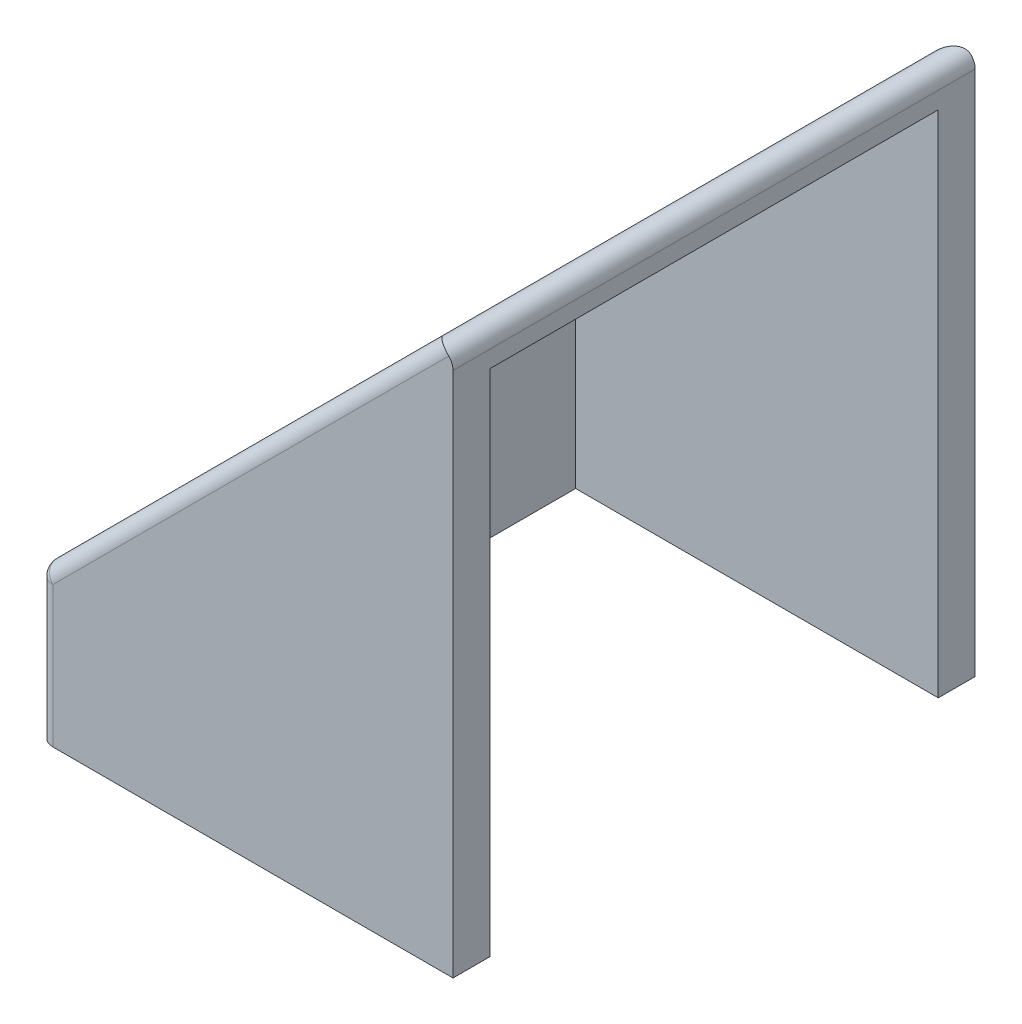
SolidWorks part; units mm, degrees
ref_plane "Front Plane" through (0, 0, 0) normal (0, 0, 1) x (1, 0, 0)
ref_plane "Top Plane" through (0, 0, 0) normal (0, 1, 0) x (1, 0, 0)
ref_plane "Right Plane" through (0, 0, 0) normal (1, 0, 0) x (0, 0, -1)
sketch "Sketch1" plane through (0, 0, 0) normal (0, 0, 1) x (1, 0, 0)
  line L0 (0, 0) -> (17.9605, 17.9605)
  line L1 (17.9605, 17.9605) -> (17.9605, 0)
  line L2 (17.9605, 0) -> (0, 0)
  dimension "D1" = 25.4
  dimension "D2" = 45
extrude "Boss-Extrude1" add sketch "Sketch1" along normal blind 22.606
sketch "Sketch2" plane through (17.9605, 0, 0) normal (1, 0, 0) x (0, 0, -1)
  line L7 (-21.006, 0) -> (-1.6, 0)
  line L10 (-1.6, 0) -> (-1.6, 16.3605)
  line L11 (-21.006, 16.3605) -> (-21.006, 0)
  line L12 (-1.6, 16.3605) -> (-21.006, 16.3605)
  line L13 (-1.6, 0) -> (-1.6, 16.3605)
  line L14 (-21.006, 16.3605) -> (-21.006, 0)
  line L15 (-1.6, 16.3605) -> (-21.006, 16.3605)
  dimension "D1" = 1.6
extrude "Cut-Extrude1" cut sketch "Sketch2" against normal offset from surface (15.6978 mm away) 1.6 up to face at (8.9803, 8.9803, 11.303)
sketch "Sketch3" plane through (0, 0, 0) normal (0, -1, 0) x (1, 0, 0)
  line L0 (17.9605, 22.606) -> (0, 22.606)
  line L1 (0, 22.606) -> (0, 0)
  line L2 (0, 0) -> (17.9605, 0)
  line L3 (17.9605, 0) -> (17.9605, 1.6)
  line L4 (17.9605, 1.6) -> (2.2627, 1.6)
  line L5 (2.2627, 1.6) -> (2.2627, 21.006)
  line L6 (2.2627, 21.006) -> (17.9605, 21.006)
  line L7 (17.9605, 21.006) -> (17.9605, 22.606)
extrude "Boss-Extrude2" add sketch "Sketch3" along normal blind 6.35
fillet "Fillet1" radius 0.635 6 edges at (17.9605, 17.9605, 11.303) (0, 0, 11.303) (8.9803, 8.9803, 0) (8.9803, 8.9803, 22.606) (0, -3.175, 0) (0, -3.175, 22.606)
